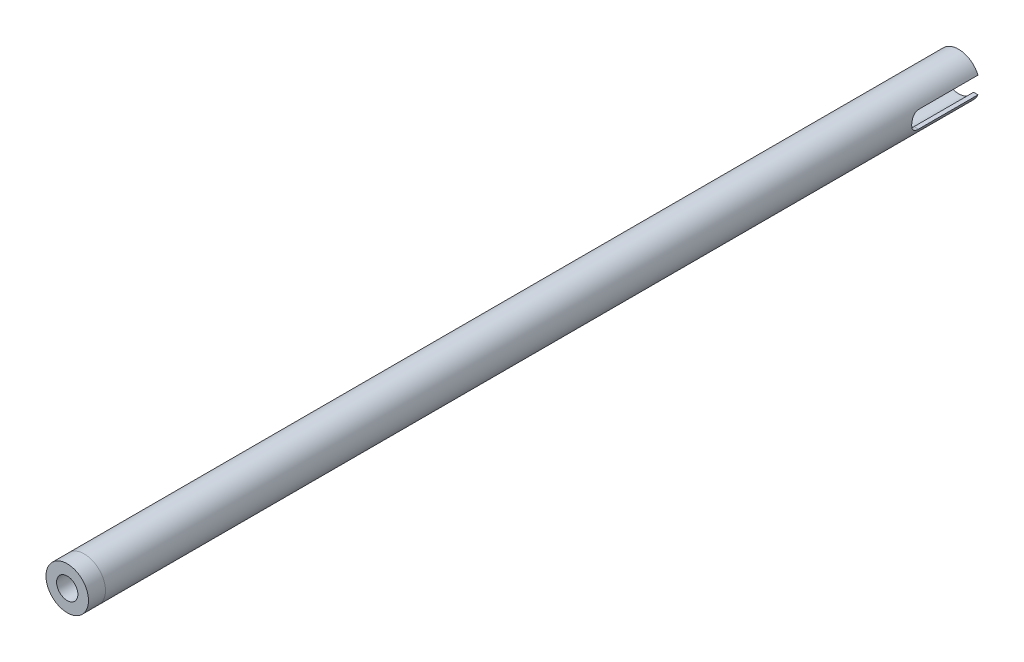
SolidWorks part; units mm, degrees
material "AISI 4130 Steel, normalized at 870C"
ref_plane "Front Plane" through (0, 0, 0) normal (0, 0, 1) x (1, 0, 0)
ref_plane "Top Plane" through (0, 0, 0) normal (0, 1, 0) x (1, 0, 0)
ref_plane "Right Plane" through (0, 0, 0) normal (1, 0, 0) x (0, 0, -1)
sketch "Axis" plane through (0, 0, 0) normal (0, 1, 0) x (1, 0, 0)
  line L0 (0, 0) -> (0, 332.6595) construction
  line L1 (0, 0) -> (0, -28.575) construction
  line L2 (0, 332.6595) -> (-7.9375, 332.6595) construction
  line L4 (0, 361.4112) -> (-10.3187, 324.0339) construction
  dimension "D1" = 28.575
  dimension "D2" = 7.9375
sketch "Sketch1" plane through (0, 0, 0) normal (0, 0, 1) x (1, 0, 0)
  line L0 (-7.9375, 0) -> (7.9375, 0) construction
  line L1 (-7.2748, 3.175) -> (7.2748, 3.175)
  line L2 (-7.2748, -3.175) -> (7.2748, -3.175)
  circle A0 centre (0, 0) radius 7.9375
  circle A1 centre (0, 0) radius 6.4643
  circle A2 centre (0, 0) radius 3.9688
  dimension "D1" = 15.875
  dimension "D3" = 7.9375
  dimension "D2" = 1.4732
  dimension "D4" = 6.35
extrude "Threaded insert 1-1" add sketch "Sketch1" against normal blind 6.35 contours A2 L1 A1 | A1 L1 A0 | A2 L0 A1 L1 | A1 L0 A0 L1 | L0 A1 L2 A0 | L0 A2 L2 A1 | A2 L2 A1 | A1 L2 A0 | L0 A1 L2 A2 | L0 A0 L2 A1 | A0 L0 A1 L1 | A1 L0 A2 L1 region at (4.8156, 1.6537, 0) region at (4.8156, -1.6537, 0) region at (6.9501, 1.6161, 0) region at (6.9501, -1.6161, 0) region at (-4.8156, -1.6537, 0) region at (-4.8156, 1.6537, 0) region at (0, 4.6361, 0) region at (0, -4.6361, 0) region at (0, 6.6174, 0) region at (6.4528, -3.3281, 0) region at (-6.9501, -1.6161, 0) region at (-6.9501, 1.6161, 0)
extrude "Threaded insert 1-2" add sketch "Sketch1<3>" against normal blind 9.525 from surface contours A2 L1 A1 | A2 L0 A1 L1 | L0 A2 L2 A1 | A2 L2 A1 | L0 A1 L2 A2 | A1 L0 A2 L1 region at (4.8156, 1.6537, 0) region at (4.8156, -1.6537, 0) region at (-4.8156, -1.6537, 0) region at (-4.8156, 1.6537, 0) region at (0, 4.6361, 0) region at (0, -4.6361, 0) starting at face at (7.9375, 0, -6.35)
sketch "Sketch1<3>" plane through (0, 0, 0) normal (0, 0, 1) x (1, 0, 0) same geometry as "Sketch1"
extrude "A-arm tube" add sketch "Sketch1<4>" against normal up to vertex (332.6595 mm away) from surface separate body contours A1 L1 A0 | A1 L0 A0 L1 | L0 A1 L2 A0 | A1 L2 A0 | L0 A0 L2 A1 | A0 L0 A1 L1 region at (6.9501, 1.6161, 0) region at (6.9501, -1.6161, 0) region at (0, 6.6174, 0) region at (6.4528, -3.3281, 0) region at (-6.9501, -1.6161, 0) region at (-6.9501, 1.6161, 0) up to point (0, 0, -332.6595) starting at face at (6.4643, 0, -6.35)
sketch "Sketch1<4>" plane through (0, 0, 0) normal (0, 0, 1) x (1, 0, 0) same geometry as "Sketch1"
extrude "Apex slot" cut sketch "Sketch1<5>" along normal blind 25.4 from surface contours A0 L0 A1 L1 | L0 A0 L2 A1 | A1 L0 A0 L1 | L0 A1 L2 A0 region at (6.9501, 1.6161, 0) region at (6.9501, -1.6161, 0) region at (-6.9501, -1.6161, 0) region at (-6.9501, 1.6161, 0) starting at face at (6.4643, 0, -332.6595)
sketch "Sketch1<5>" plane through (0, 0, 0) normal (0, 0, 1) x (1, 0, 0) same geometry as "Sketch1"
fillet "Fillet1" radius 3.175 4 edges at (-6.4528, 3.175, -307.2595) (-6.4528, -3.175, -307.2595) (6.4528, -3.175, -307.2595) (6.4528, 3.175, -307.2595)
equation "\"tube diameter\"= 5 / 8"
equation "\"tube thickness\"= .058"
equation "\"apex thickness\"= .25"
equation "\"tube slot\"= 1"
equation "\"D1@Sketch1\"=\"tube diameter\""
equation "\"D2@Sketch1\"=\"tube thickness\""
equation "\"threaded insert hole\"= .3125"
equation "\"D3@Sketch1\"=\"threaded insert hole\""
equation "\"D4@Sketch1\"=\"apex thickness\""
equation "\"D1@Apex slot\" = \"tube slot\""
equation "\"D1@Fillet1\"=\"apex thickness\"/2"
equation "\"D2@Axis\"=\"tube diameter\"/2"
